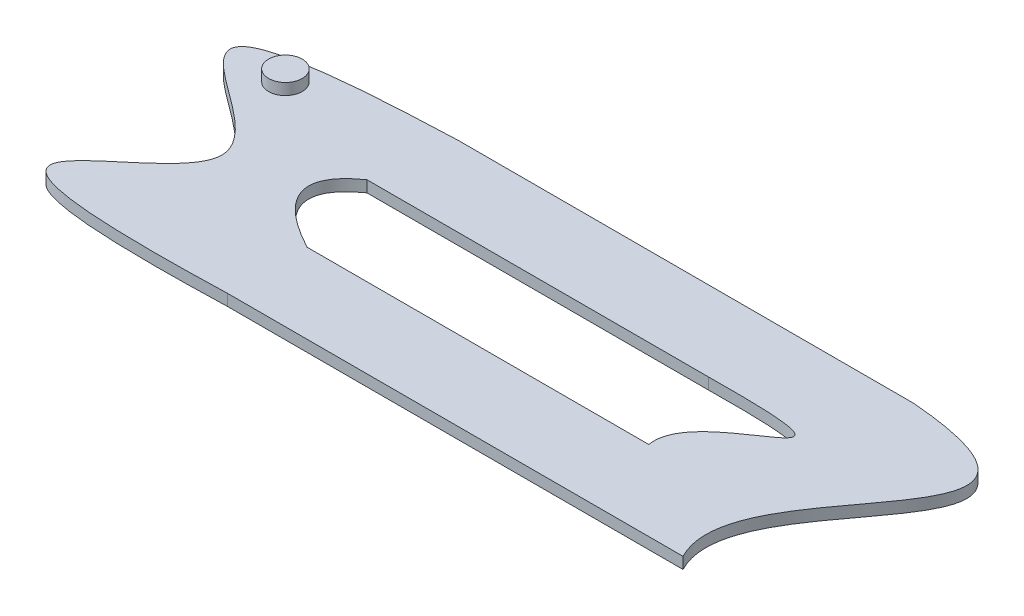
SolidWorks part; units mm, degrees
ref_plane "Front Plane" through (0, 0, 0) normal (0, 0, 1) x (1, 0, 0)
ref_plane "Top Plane" through (0, 0, 0) normal (0, 1, 0) x (1, 0, 0)
ref_plane "Right Plane" through (0, 0, 0) normal (1, 0, 0) x (0, 0, -1)
sketch "Sketch1" plane through (0, 0, 0) normal (0, 1, 0) x (1, 0, 0)
  line L4 (-6181.0002, 1570.9863) -> (13818.9998, 1570.9863)
  line L5 (-6681.4538, -1929.0137) -> (8318.5462, -1929.0137)
  line L6 (-5428.6427, -5807.5795) -> (9571.3573, -5807.5795)
  line L7 (-5425.8812, -9307.5795) -> (14574.1188, -9307.5795)
  spline S0 degree 2 poles (-6681.4538, -1929.0137) (-9266.0055, -3764.962) (-5428.6427, -5807.5795) knots 0 0 0 1 1 1
  spline S1 degree 3 poles (8318.5462, -1929.0137) (17100.5972, -1833.8772) (9076.0459, -3004.7586) (9571.3573, -5807.5795) knots 0 0 0 0 1 1 1 1
  spline S2 degree 3 poles (-6181.0002, 1570.9863) (-22070.4309, 1028.6428) (23.7912, -3734.0826) (-21201.0494, -9802.0922) (-5425.8812, -9307.5795) knots 0 0 0 0 0.51432 1 1 1 1
  spline S3 degree 3 poles (13818.9998, 1570.9863) (24199.0306, 720.0053) (12166.4563, -4701.9167) (14574.1188, -9307.5795) knots 0 0 0 0 1 1 1 1
  point P14 (15451.596, -4871.4317)
  dimension "D5" = 3500
  dimension "D1" = 20000
  dimension "D2" = 15000
  dimension "D3" = 15000
  dimension "D4" = 20000
  dimension "D6" = 3500
extrude "Boss-Extrude1" add sketch "Sketch1" along normal blind 500
sketch "Sketch2" plane through (0, 500, 0) normal (0, 1, 0) x (1, 0, 0)
  circle A0 centre (-12186.7495, 0) radius 737.132
  dimension "D1" = 1474.2639
extrude "Boss-Extrude2" add sketch "Sketch2" along normal blind 500
